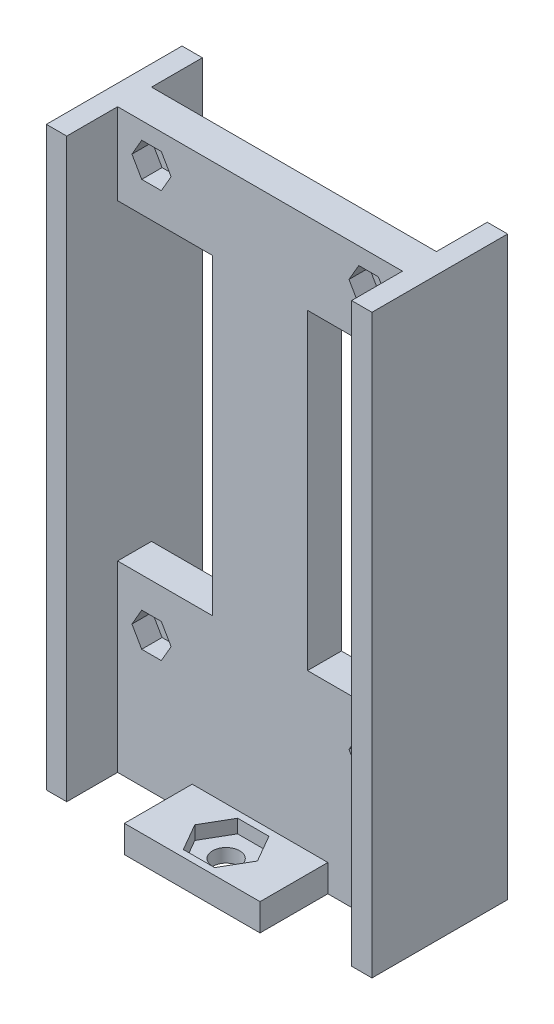
SolidWorks part; units mm, degrees
ref_plane "Front Plane" through (0, 0, 0) normal (0, 0, 1) x (1, 0, 0)
ref_plane "Top Plane" through (0, 0, 0) normal (0, 1, 0) x (1, 0, 0)
ref_plane "Right Plane" through (0, 0, 0) normal (1, 0, 0) x (0, 0, -1)
sketch "Sketch1" plane through (0, 0, 0) normal (0, 0, 1) x (1, 0, 0)
  line L0 (-10.5, 11.5) -> (-3.5, 11.5)
  line L1 (-10.5, -17.5) -> (10.5, -17.5)
  line L2 (-10.5, -17.5) -> (-10.5, 17.5)
  line L3 (-10.5, 17.5) -> (10.5, 17.5)
  line L4 (10.5, -17.5) -> (10.5, 17.5)
  line L5 (0, 17.5) -> (0, -17.5) construction
  line L6 (-10.5, 0) -> (10.5, 0) construction
  line L7 (-3.5, 11.5) -> (-3.5, -11.5)
  line L8 (3.5, 11.5) -> (3.5, -11.5)
  line L9 (10.5, 11.5) -> (3.5, 11.5)
  line L10 (10.5, -11.5) -> (3.5, -11.5)
  line L11 (-10.5, -11.5) -> (-3.5, -11.5)
  circle A0 centre (-8, 15) radius 0.8
  circle A1 centre (8, 15) radius 0.8
  circle A2 centre (8, -15) radius 0.8
  circle A3 centre (-8, -15) radius 0.8
  point P0 (0, 0)
  point P20 (3.5, 0)
  point P21 (-3.5, 0)
  dimension "D5" = 1.6
  dimension "D1" = 35
  dimension "D2" = 21
  dimension "D3" = 8
  dimension "D4" = 15
  dimension "D6" = 6
  dimension "D7" = 3.5
extrude "BracketWithBoltHoles" add sketch "Sketch1" along normal blind 2.5 contours L11 L2 L1 L4 L10 L8 L9 L3 L0 L7 A1 A0 A2 A3 region at (0, 0, 0)
sketch "Sketch2" plane through (0, 0, 2.5) normal (0, 0, 1) x (1, 0, 0)
  line L1 (-10.5, -17.5) -> (10.5, -17.5)
  line L2 (-10.5, -17.5) -> (-10.5, -25)
  line L3 (-10.5, -25) -> (10.5, -25)
  line L4 (10.5, -17.5) -> (10.5, -25)
  line L5 (-5, -25) -> (5, -25)
  line L6 (-5, -25) -> (-5, -23)
  line L7 (-5, -23) -> (5, -23)
  line L8 (5, -25) -> (5, -23)
  line L9 (0, -23) -> (0, -25) construction
  line L10 (-5, -24) -> (5, -24) construction
  circle A0 centre (8, 15) radius 0.8 construction
  circle A1 centre (8, 15) radius 0.8 construction
  point P8 (0, -24)
  point P15 (0, -25)
  line M8 (-10.5, -17.5) -> (10.5, -17.5)
  dimension "D1" = 40
  dimension "D2" = 10
  dimension "D3" = 2
extrude "BracketExtension" add sketch "Sketch2" against normal up to surface (2.5 mm away) contours L8 L3 L4 L2 L6 L7 M8 | L3 L8 L7 L6 region at (0, -20.85, 2.5) region at (0, -24, 2.5) up to face at (8.8, 15, 0)
extrude "Base" add sketch "Sketch2<3>" along normal blind 5 and the other way blind 7.5 contours L3 L8 L7 L6 region at (0, -24, 2.5)
sketch "Sketch2<3>" plane through (0, 0, 2.5) normal (0, 0, 1) x (1, 0, 0) same geometry as "Sketch2"
sketch "Sketch3" plane through (0, -23, 0) normal (0, 1, 0) x (1, 0, 0)
  line L0 (0, -7.5) -> (0, -2.5) construction
  line L1 (-5, -7.5) -> (5, -7.5) construction
  line L2 (-5, -2.5) -> (5, -2.5) construction
  line L3 (-10.5, -1.25) -> (10.5, -1.25) construction
  line L4 (-10.5, -2.5) -> (-10.5, 0) construction
  line L5 (10.5, -2.5) -> (10.5, 0) construction
  line L11 (-2.3094, 2.5) -> (-1.1547, 4.5)
  line L12 (1.1547, -3) -> (-1.1547, -3)
  line L16 (-1.1547, -3) -> (-2.3094, -5)
  line L17 (-2.3094, -5) -> (-1.1547, -7)
  line L18 (-1.1547, -7) -> (1.1547, -7)
  line L19 (1.1547, -7) -> (2.3094, -5)
  line L20 (2.3094, -5) -> (1.1547, -3)
  line L21 (-1.1547, 4.5) -> (1.1547, 4.5)
  line L22 (1.1547, 4.5) -> (2.3094, 2.5)
  line L23 (2.3094, 2.5) -> (1.1547, 0.5)
  line L24 (1.1547, 0.5) -> (-1.1547, 0.5)
  line L25 (-1.1547, 0.5) -> (-2.3094, 2.5)
  circle A0 centre (0, -5) radius 1
  circle A1 centre (0, 2.5) radius 1
  circle A2 centre (0, -5) radius 2 construction
  dimension "D2" = 4
extrude "BaseBoltHoles" cut sketch "Sketch3" against normal through all contours A0 | A1 region at (0, -23, 5) region at (0, -23, -2.5)
extrude "BaseNutSlots" cut sketch "Sketch3<3>" against normal blind 1 contours L19 L20 L12 L16 L17 L18 A0 | L25 L24 L23 L22 L21 L11 A1 | A0 region at (-1.6791, -23, -3.4694) region at (1.6791, -23, 4.0306)
sketch "Sketch3<3>" plane through (0, -23, 0) normal (0, 1, 0) x (1, 0, 0) same geometry as "Sketch3"
sketch "Sketch4" plane through (0, 17.5, 0) normal (0, 1, 0) x (1, 0, 0)
  line L0 (-10.5, -2.5) -> (-10.5, 0) construction
  line L5 (-12, 3.75) -> (-10.5, 3.75)
  line L6 (-12, 3.75) -> (-12, -6.25)
  line L7 (-12, -6.25) -> (-10.5, -6.25)
  line L8 (-10.5, 3.75) -> (-10.5, -6.25)
  line L9 (-11.25, -6.25) -> (-11.25, 3.75) construction
  line L10 (-12, -1.25) -> (-10.5, -1.25) construction
  line L11 (-10.5, -2.5) -> (-10.5, 0) construction
  point P0 (-11.25, -1.25)
  point P9 (-10.5, -1.25)
  dimension "D1" = 1.5
  dimension "D2" = 10
extrude "StiffenerRib" add sketch "Sketch4" against normal up to surface (42.5 mm away) up to face at (0, -25, -1.5)
mirror "StiffenerRib2" about plane through (0, 0, 0) normal (1, 0, 0) of "StiffenerRib"
sketch "Sketch5" plane through (0, 0, 2.5) normal (0, 0, 1) x (1, 0, 0)
  line L0 (0, 0) -> (0, 9.2184) construction
  line L5 (-7.2783, 16.25) -> (-8.7217, 16.25)
  line L6 (-8.7217, 16.25) -> (-9.4434, 15)
  line L11 (-9.4434, 15) -> (-8.7217, 13.75)
  line L12 (-8.7217, 13.75) -> (-7.2783, 13.75)
  line L17 (-7.2783, 13.75) -> (-6.5566, 15)
  line L18 (-6.5566, 15) -> (-7.2783, 16.25)
  line L23 (-7.2783, -13.75) -> (-8.7217, -13.75)
  line L24 (-8.7217, -13.75) -> (-9.4434, -15)
  line L25 (-9.4434, -15) -> (-8.7217, -16.25)
  line L26 (-8.7217, -16.25) -> (-7.2783, -16.25)
  line L27 (-7.2783, -16.25) -> (-6.5566, -15)
  line L28 (-6.5566, -15) -> (-7.2783, -13.75)
  line L29 (8.7217, -16.25) -> (7.2783, -16.25)
  line L30 (9.4434, -15) -> (8.7217, -16.25)
  line L31 (8.7217, -13.75) -> (9.4434, -15)
  line L32 (7.2783, -13.75) -> (8.7217, -13.75)
  line L33 (6.5566, -15) -> (7.2783, -13.75)
  line L34 (7.2783, -16.25) -> (6.5566, -15)
  line L35 (6.5566, 15) -> (7.2783, 16.25)
  line L36 (7.2783, 16.25) -> (8.7217, 16.25)
  line L37 (8.7217, 16.25) -> (9.4434, 15)
  line L38 (9.4434, 15) -> (8.7217, 13.75)
  line L39 (8.7217, 13.75) -> (7.2783, 13.75)
  line L40 (7.2783, 13.75) -> (6.5566, 15)
  circle A3 centre (-8, 15) radius 0.8 construction
  circle A7 centre (-8, 15) radius 0.8 construction
  circle A8 centre (-8, 15) radius 1.25 construction
  circle A9 centre (-8, -15) radius 0.8 construction
  circle A10 centre (-8, -15) radius 0.8 construction
  circle A11 centre (-8, -15) radius 1.25 construction
  dimension "D1" = 2.5
  dimension "D2" = 2.5
extrude "BracketNutSlots" cut sketch "Sketch5" against normal blind 1.5
equation "\"BoltD\"=2mm"
equation "\"BoltHatD\"=3.2mm"
equation "\"NutShortSide\"=4mm"
equation "\"NutLongSide\"=4.5mm"
equation "\"SmallScrewD\"=1.2mm"
equation "\"SmallScrewHatD\"=2mm"
equation "\"TubeOuterD\"=1.2mm"
equation "\"TubeClipW\"=1.5mm"
equation "\"TubeClipH\"=1.5mm"
equation "\"TubeClipLock_SideL\"=1.5mm"
equation "\"TubeClipLock_W\"=0.7mm"
equation "\"BasicPulleyD\"=15mm"
equation "\"GrooveDepth\"=0.7mm"
equation "\"Cable1D\"=0.4mm"
equation "\"Cable2D\"=0.3mm"
equation "\"BallBearingInnerD\"=2mm"
equation "\"BallBearingOuterD\"=4mm"
equation "\"BallBearingThickness\"=2mm"
equation "\"BearingCapD\"=12mm"
equation "\"HumerusL\"=37.2mm"
equation "\"HumerusElbowSidePulleyD\"=10mm"
equation "\"RadiusL\"=68.1mm"
equation "\"Finger1L\"=120mm"
equation "\"Finger2L\"=100mm"
equation "\"Finger3L\"=80mm"
equation "\"ElbowExtendedAngle\"=140deg"
equation "\"ElbowFlexedAngle\"=38deg"
equation "\"Digit5ExtendedAngle\"=80deg"
equation "\"Digit5FlexedAngle\"=24deg"
equation "\"Digit4ExtendedAngle\"=108deg"
equation "\"Digit4FlexedAngle\"=34deg"
equation "\"Digit3ExtendedAngle\"=145deg"
equation "\"Digit3FlexedAngle\"=44deg"
equation "\"KST_ServoBoltShelfHeight\"=21.1mm"
equation "\"KST_ServoLength\"=23mm"
equation "\"KST_ServoWidth\"=12mm"
equation "\"KST_ServoBoltHole2HoleLength\"=28mm"
equation "\"KST_ServoBoltHole2ShaftDist\"=8.3mm"
equation "\"KST_ServoBoltHole2HoleWidth\"=7mm"
equation "\"KST_ServoHeight\"=27.5mm"
equation "\"KST_ServoShaftHeight\"=3.5mm"
equation "\"KST_ServoShaftD\"=4.25mm"
equation "\"KST_ServoShaftToothL\"=0.345mm"
equation "\"KST_ServoShaftToothAngle\"=60deg"
equation "\"KST_ServoShaftToothTipWidth\"=0.18mm"
equation "\"KST_ServoShaftToothFilletR\"=0.1mm"
equation "\"KST_ServoShaftToothN\"=25"
equation "\"KST_ServoShaftBoltD\"=2mm"
equation "\"KST_ServoShaftBoltHatD\"=5mm"
equation "\"XL330_M077_T_Length\"=34mm"
equation "\"XL330_M077_T_Width\"=20mm"
equation "\"XL330_M077_T_Height\"=23mm"
equation "\"XL330_M077_T_BoltHole2HoleLength\"=30mm"
equation "\"XL330_M077_T_BoltHole2HoleWidth\"=16mm"
equation "\"XL330_M077_T_BoltHole2ShaftDist\"=7.5mm"
equation "\"XL330_M077_T_HornHeight\"=3mm"
equation "\"XL330_M077_T_HornScrewHoleCircleD\"=12mm"
equation "\"D1@Sketch1\"=\"XL330_M077_T_Length\"+1"
equation "\"D2@Sketch1\"=\"XL330_M077_T_Width\"+1"
equation "\"D3@Sketch1\"=\"XL330_M077_T_BoltHole2HoleWidth\"/2"
equation "\"D4@Sketch1\"=\"XL330_M077_T_BoltHole2HoleLength\"/2"
equation "\"D1@Sketch2\"=\"XL330_M077_T_BoltHole2ShaftDist\"+32.5"
equation "\"D1@Sketch3\"=\"BoltD\""
equation "\"XL330_M077_T_BoltD\"=1.6mm"
equation "\"D5@Sketch1\"=\"XL330_M077_T_FrameBoltD\""
equation "\"XL330_M077_T_FrameBoltD\"=1.6mm"
equation "\"XL330_M077_T_FrameNutShortSide\"=2.5mm"
equation "\"XL330_M077_T_FrameNutLongSide\"=3mm"
equation "\"XL330_M077_T_HornD\"=16mm"
equation "\"XL330_M077_T_FrameBoltHatD\"=3mm"
equation "\"XL330_M077_T_HornScrewD\"=1.9mm"
equation "\"XL330_M077_T_HornScrewHatD\"=3.3mm"
equation "\"D2@Sketch3\"=\"NutShortSide\""
equation "\"D1@Sketch5\"=\"XL330_M077_T_FrameNutShortSide\""
equation "\"D2@Sketch5\"=\"D1@Sketch5\""
